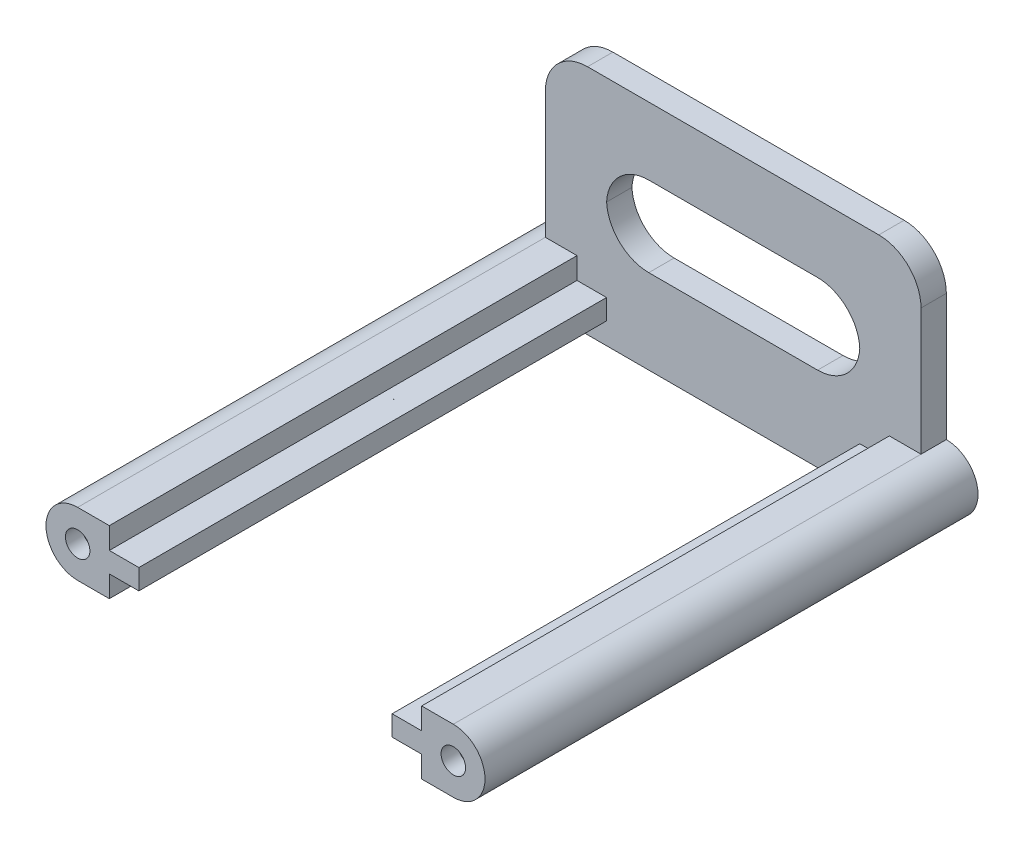
SolidWorks part; units mm, degrees
ref_plane "前视基准面" through (0, 0, 0) normal (0, 0, 1) x (1, 0, 0)
ref_plane "上视基准面" through (0, 0, 0) normal (0, 1, 0) x (1, 0, 0)
ref_plane "右视基准面" through (0, 0, 0) normal (1, 0, 0) x (0, 0, -1)
sketch "草图1" plane through (0, 0, 0) normal (0, 0, 1) x (1, 0, 0)
  line L0 (-0.3, 0.0836) -> (45.7717, 0.0836) construction
  line L2 (18.5, 3.8336) -> (22.25, 3.8336)
  line L3 (18.5, 3.8336) -> (18.5, -3.6664)
  line L4 (18.5, -3.6664) -> (22.25, -3.6664)
  line L9 (15, 1.2836) -> (18.5, 1.2836)
  line L10 (15, 1.2836) -> (15, -1.1164)
  line L11 (15, -1.1164) -> (18.5, -1.1164)
  line L12 (18.5, 1.2836) -> (18.5, -1.1164)
  circle A0 centre (22.25, 0.0836) radius 2.75
  circle A1 centre (22.25, 0.0836) radius 3.75
  circle A2 centre (22.25, 0.0836) radius 1.45
  point P2 (15, 0.0836)
  point P8 (26, 0.0836)
  point P11 (46.0717, 0)
  point P12 (20.375, 3.8336)
  point P14 (20.375, -3.6664)
  dimension "D2" = 5.5
  dimension "D6" = 2.9
  dimension "D3" = 7.5
  dimension "D4" = 26
  dimension "D5" = 2.4
  dimension "D7" = 15
  dimension "D8" = 18.5
  dimension "D9" = 22.25
  dimension "D1" = 1
extrude "拉伸1" add sketch "草图1" against normal blind 55.4 contours L0 A1 A0 | A1 L0 A0 | A1 L2 L3 | A1 L12 L3 L4 | L0 L10 L11 L12 | L10 L0 L3 L9 region at (22.25, 2.9175, 0) region at (25.5, -0.0002, 0) region at (19.3376, 2.996, 0) region at (19.3376, -2.8288, 0) region at (16.75, -0.5164, 0) region at (16.75, 0.6836, 0)
extrude "拉伸2" add sketch "草图1<3>" against normal blind 2 contours L0 A0 A2 | A0 L0 A2 region at (22.25, 1.5951, 0) region at (24.35, 0.0221, 0)
sketch "草图1<3>" plane through (0, 0, 0) normal (0, 0, 1) x (1, 0, 0) same geometry as "草图1"
sketch "草图2" plane through (0, 0, -55.4) normal (0, 0, -1) x (-1, 0, 0)
  line L0 (0, 0) -> (0, -5.8178) construction
  line L1 (-18.5, -3.6664) -> (0, -3.6664)
  line L2 (-22.25, 3.8336) -> (-22.25, 23.8336)
  line L3 (-22.25, 23.8336) -> (0, 23.8336)
  line L4 (-15, 6.3336) -> (-15, 15.8336)
  line L5 (-15, 15.8336) -> (0, 15.8336)
  line L6 (-15, 6.3336) -> (0, 6.3336)
  line L7 (-22.25, -3.6664) -> (-18.5, -3.6664)
  line L8 (-18.5, -3.6664) -> (-18.5, -1.1164)
  line L9 (-18.5, -1.1164) -> (-15, -1.1164)
  line L10 (-15, -1.1164) -> (-15, 1.2836)
  line L11 (-15, 1.2836) -> (-18.5, 1.2836)
  line L12 (-18.5, 1.2836) -> (-18.5, 3.8336)
  line L13 (-18.5, 3.8336) -> (-22.25, 3.8336)
  line L14 (-22.25, -3.6664) -> (-18.5, -3.6664)
  line L15 (-21.25, 4.7272) -> (-21.25, 22.8336)
  line L16 (-21.25, 22.8336) -> (-1, 22.8336)
  line L17 (-1, 22.8336) -> (-1, 16.8336)
  line L18 (-16, 16.8336) -> (-1, 16.8336)
  line L19 (-16, 5.3336) -> (-16, 16.8336)
  line L20 (-16, 5.3336) -> (-1, 5.3336)
  line L21 (0, 23.8336) -> (0, 15.8336)
  line L22 (0, 6.3336) -> (0, -3.6664)
  line L23 (-1, 5.3336) -> (-1, -2.6664)
  line L24 (-18.5, -2.6664) -> (-1, -2.6664)
  line L25 (-1, 5.3336) -> (0, 5.3336)
  line L26 (-21.25, 2.6453) -> (-21.25, 22.8336) construction
  line L27 (-22.25, -2.6664) -> (-18.5, -2.6664) construction
  line L28 (-1, -2.6664) -> (0, -2.6664)
  arc A0 (-22.25, 3.8336) -> (-21.25, 3.6978) centre (-22.25, 0.0836) ccw
  arc A1 (-22.25, 3.8336) -> (-22.25, -3.6664) centre (-22.25, 0.0836) ccw
  arc A2 (-22.25, 3.8336) -> (-22.25, -3.6664) centre (-22.25, 0.0836) ccw
  arc A3 (-21.25, 2.6453) -> (-22.25, -2.6664) centre (-22.25, 0.0836) ccw
  circle A4 centre (-22.25, 0.0836) radius 2.75
  arc A5 (-18.377, -2.6664) -> (-21.25, 4.7272) centre (-22.25, 0.0836) ccw
  circle A6 centre (-22.25, 0.0836) radius 4.75 construction
  circle A7 centre (-22.25, 0.0836) radius 3.75 construction
  circle A8 centre (-22.25, 0.0836) radius 3.75
  circle M9 centre (-22.25, 0.0836) radius 2.75
  arc M10 (-22.25, 3.8336) -> (-22.25, -3.6664) centre (-22.25, 0.0836) ccw
  line M11 (-22.25, -3.6664) -> (-18.5, -3.6664)
  line M12 (-18.5, -3.6664) -> (-18.5, -1.1164)
  line M13 (-18.5, -1.1164) -> (-15, -1.1164)
  line M14 (-15, -1.1164) -> (-15, 1.2836)
  line M15 (-15, 1.2836) -> (-18.5, 1.2836)
  line M16 (-18.5, 1.2836) -> (-18.5, 3.8336)
  line M17 (-18.5, 3.8336) -> (-22.25, 3.8336)
  dimension "D2" = 22.25
  dimension "D3" = 10
  dimension "D4" = 27.5
  dimension "D5" = 8
  dimension "D1" = 0
  dimension "D6" = 1
  dimension "D7" = 1
extrude "拉伸4" add sketch "草图2" along normal blind 2 contours A5 L15 L16 L17 L18 L19 L20 L25 L22 L6 L4 L5 L21 L3 L2 M17 | A5 L24 L23 L20 L19 L18 L17 L16 L15 M15 M14 M13 M17 M16 | L23 L28 L22 L25 | A5 M15 M16 | L24 A5 M13 M12 | A5 M13 M14 M15 | A8 A0 A5 M11 M12 M13 M15 M16 M17 | A0 A8 M10 M9 | L28 L24 L1 L22 M12 | A5 M16 M17 region at (9.25, -3.1664, -55.4) region at (20.375, -3.5776, -55.4) region at (25.8939, 0.0836, -55.4) region at (18.189, -1.7204, -55.4) region at (0.5, 1.3336, -55.4) region at (21.9508, 13.8336, -55.4) region at (17.6501, -2.0618, -55.4) region at (18.7665, 3.5671, -55.4) region at (16.2759, 0.0836, -55.4) region at (18.1923, 1.8998, -55.4)
extrude "拉伸6" add sketch "草图2<3>" along normal blind 3 contours A5 L15 L16 L17 L18 L19 L20 L25 L22 L6 L4 L5 L21 L3 L2 M17 | A8 A0 A5 M11 M12 M13 M15 M16 M17 | A5 M15 M16 | L24 A5 M13 M12 | L28 L24 L1 L22 M12 | L23 L28 L22 L25 | A0 A8 M10 M9 region at (9.25, -3.1664, -55.4) region at (20.375, -3.5776, -55.4) region at (25.8939, 0.0836, -55.4) region at (18.189, -1.7204, -55.4) region at (0.5, 1.3336, -55.4) region at (21.9508, 13.8336, -55.4) region at (18.1923, 1.8998, -55.4)
sketch "草图2<3>" plane through (0, 0, -55.4) normal (0, 0, -1) x (-1, 0, 0) same geometry as "草图2"
fillet "圆角1" radius 5 6 edges at (16, 5.3336, -57.9) (16, 16.8336, -57.9) (21.25, 22.8336, -57.9) (15, 6.3336, -56.9) (15, 15.8336, -56.9) (22.25, 23.8336, -56.9)
mirror "镜向2" about plane through (0, 0, 0) normal (1, 0, 0) of "圆角1", "拉伸6", "拉伸4"
mirror "镜向3" about plane through (0, 0, 0) normal (1, 0, 0) of "拉伸2", "拉伸1"
